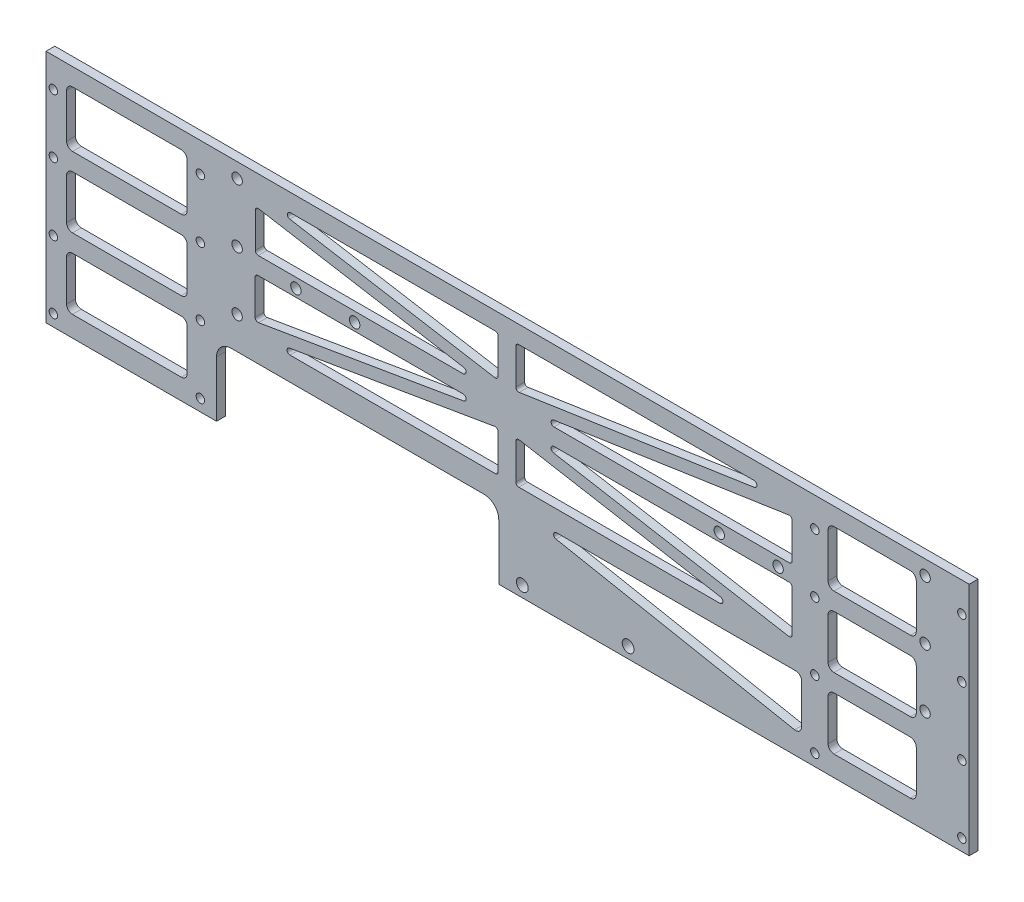
SolidWorks part; units mm, degrees
material "6061-T6 (SS)"
ref_plane "Front Plane" through (0, 0, 0) normal (0, 0, 1) x (1, 0, 0)
ref_plane "Top Plane" through (0, 0, 0) normal (0, 1, 0) x (1, 0, 0)
ref_plane "Right Plane" through (0, 0, 0) normal (1, 0, 0) x (0, 0, -1)
sketch "Sketch1" plane through (0, 0, 0) normal (0, 0, 1) x (1, 0, 0)
  line L1 (-199.39, 50.8) -> (199.39, 50.8)
  line L2 (-199.39, 50.8) -> (-199.39, -50.8)
  line L3 (-199.39, -50.8) -> (199.39, -50.8)
  line L4 (199.39, 50.8) -> (199.39, -50.8)
  line L5 (-199.39, 50.8) -> (199.39, -50.8) construction
  line L6 (-199.39, -50.8) -> (199.39, 50.8) construction
  point P0 (0, 0)
  dimension "D1" = 101.6
  dimension "D2" = 398.78
extrude "Boss-Extrude1" add sketch "Sketch1" along normal blind 3.81
sketch "Sketch11" plane through (0, 0, 3.81) normal (0, 0, 1) x (1, 0, 0)
  line L0 (-199.39, -50.8) -> (199.39, -50.8) construction
  line L1 (-125.73, -50.8) -> (-3.81, -50.8)
  line L2 (-125.73, -50.8) -> (-125.73, -20.32)
  line L3 (-125.73, -20.32) -> (-3.81, -20.32)
  line L4 (-3.81, -50.8) -> (-3.81, -20.32)
  line L5 (-199.39, 50.8) -> (-199.39, -50.8) construction
  line L6 (199.39, -50.8) -> (199.39, 50.8) construction
  dimension "D1" = 30.48
  dimension "D2" = 73.66
  dimension "D3" = 203.2
extrude "Cut-Extrude1" cut sketch "Sketch11" against normal through all
sketch "Sketch15" plane through (0, 0, 3.81) normal (0, 0, 1) x (1, 0, 0)
  line L0 (199.39, 50.8) -> (-199.39, 50.8) construction
  line L1 (91.44, 16.0648) -> (116.84, 16.0648) construction
  line L2 (180.34, 44.45) -> (180.34, -6.35) construction
  line L3 (199.39, -50.8) -> (199.39, 50.8) construction
  line L4 (199.39, 50.8) -> (-199.39, 50.8) construction
  line L5 (-199.39, 50.8) -> (-199.39, -50.8) construction
  line L6 (-66.04, 16.0648) -> (-91.44, 16.0648) construction
  line L7 (6.35, -46.0375) -> (52.07, -46.0375) construction
  line L8 (-3.81, -50.8) -> (199.39, -50.8) construction
  line L9 (-3.81, -50.8) -> (-3.81, -20.32) construction
  point P0 (196.215, 38.1)
  point P1 (196.215, 12.7)
  point P2 (196.215, -16.51)
  point P3 (196.215, -45.72)
  point P9 (132.715, -45.72)
  point P10 (180.34, 19.05)
  point P11 (132.715, -15.24)
  point P12 (132.715, 15.24)
  point P13 (132.715, 45.72)
  point P17 (91.44, 16.0648)
  point P20 (116.84, 16.0648)
  dimension "D1" = 63.5
  dimension "D2" = 3.175
  dimension "D3" = 29.21
  dimension "D4" = 29.21
  dimension "D5" = 25.4
  dimension "D6" = 5.08
  dimension "D7" = 30.48
  dimension "D8" = 30.48
  dimension "D9" = 30.48
  dimension "D10" = 19.05
  dimension "D11" = 50.8
  dimension "D12" = 6.35
  dimension "D13" = 25.4
  dimension "D14" = 34.7352
  dimension "D15" = 15.875
  dimension "D16" = 107.95
  dimension "D17" = 45.72
  dimension "D18" = 4.7625
  dimension "D19" = 10.16
hole_wizard "#6 Clearance Hole1" positions "Sketch19" profile "Sketch20" hole size "#6" standard "ANSI Inch" end condition through all
sketch "Sketch19" plane through (0, 0, 3.81) normal (0, 0, 1) x (1, 0, 0)
  line L0 (199.39, 50.8) -> (-199.39, 50.8) construction
  line L1 (199.39, -50.8) -> (199.39, 50.8) construction
  line L2 (-199.39, 50.8) -> (-199.39, -50.8) construction
  point P55 (132.715, -45.72)
  point P58 (196.215, -45.72)
  point P63 (132.715, 12.7)
  point P65 (132.715, -16.51)
  point P67 (196.215, 38.1)
  point P71 (196.215, -16.51)
  point P84 (-196.215, 38.1)
  point P86 (-196.215, 12.7)
  point P88 (-196.215, -16.51)
  point P90 (-196.215, -45.72)
  point P95 (-132.715, 38.1)
  point P97 (-132.715, 12.7)
  point P99 (-132.715, -16.51)
  point P101 (-132.715, -45.72)
  point P113 (196.215, 12.7)
  point P116 (132.715, 38.1)
  dimension "D2" = 12.7
  dimension "D3" = 29.21
  dimension "D4" = 25.4
  dimension "D5" = 29.21
  dimension "D6" = 25.4
  dimension "D7" = 29.21
  dimension "D8" = 29.21
  dimension "D9" = 3.175
  dimension "D10" = 12.7
  dimension "D11" = 12.7
  dimension "D12" = 25.4
  dimension "D13" = 29.21
  dimension "D14" = 29.21
  dimension "D15" = 3.175
  dimension "D16" = 12.7
  dimension "D17" = 25.4
  dimension "D18" = 29.21
  dimension "D19" = 29.21
  dimension "D20" = 66.675
  dimension "D21" = 66.675
sketch "Sketch20" plane through (132.715, -45.72, 3.81) normal (1, 0, 0) x (0, -1, 0)
  line L0 (0, 0) -> (0, 3.81)
  line L1 (0, 3.81) -> (1.8288, 3.81)
  line L2 (1.8288, 3.81) -> (1.8288, 0)
  line L5 (1.8288, 0) -> (0, 0)
  line L11 (0, -6.35) -> (0, 107.95) construction
  dimension "Thru Hole Dia." = 3.6576
  dimension "Thru Hole Depth" = 3.81
hole_wizard "#8 Clearance Hole1" positions "Sketch24" profile "Sketch25" hole size "#8" standard "ANSI Inch" end condition through all
sketch "Sketch24" plane through (0, 0, 3.81) normal (0, 0, 1) x (1, 0, 0)
  line L0 (-199.39, 50.8) -> (-199.39, -50.8) construction
  point P0 (180.34, 44.45)
  point P3 (180.34, 19.05)
  point P6 (180.34, -6.35)
  point P10 (-116.84, 44.45)
  point P12 (-116.84, 19.05)
  point P14 (-116.84, -6.35)
  point P23 (91.44, 16.0648)
  point P26 (116.84, 16.0648)
  point P29 (-91.44, 16.0648)
  point P32 (-66.04, 16.0648)
  dimension "D1" = 82.55
sketch "Sketch25" plane through (180.34, 44.45, 3.81) normal (1, 0, 0) x (0, -1, 0)
  line L0 (0, 0) -> (0, 3.81)
  line L1 (0, 3.81) -> (2.2479, 3.81)
  line L2 (2.2479, 3.81) -> (2.2479, 0)
  line L5 (2.2479, 0) -> (0, 0)
  line L11 (0, -6.35) -> (0, 107.95) construction
  dimension "Thru Hole Dia." = 4.4958
  dimension "Thru Hole Depth" = 3.81
fillet "Fillet1" radius 6.35 2 edges at (-125.73, -20.32, 1.905) (-3.81, -20.32, 1.905)
hole_wizard "#7 (0.201) Diameter Hole1" positions "Sketch26" profile "Sketch27" hole size "#7" standard "ANSI Inch" end condition through all
sketch "Sketch26" plane through (0, 0, 3.81) normal (0, 0, 1) x (1, 0, 0)
  point P0 (6.35, -46.0375)
  point P3 (52.07, -46.0375)
sketch "Sketch27" plane through (6.35, -46.0375, 3.81) normal (1, 0, 0) x (0, -1, 0)
  line L0 (0, 0) -> (0, 3.81)
  line L1 (0, 3.81) -> (2.5527, 3.81)
  line L2 (2.5527, 3.81) -> (2.5527, 0)
  line L5 (2.5527, 0) -> (0, 0)
  line L11 (0, -6.35) -> (0, 107.95) construction
  dimension "Thru Hole Dia." = 5.1054
  dimension "Thru Hole Depth" = 3.81
sketch "Sketch28" plane through (0, 0, 3.81) normal (0, 0, 1) x (1, 0, 0)
  line L0 (199.39, 50.8) -> (-199.39, 50.8) construction
  line L1 (-187.96, 43.18) -> (-140.97, 43.18)
  line L2 (-190.5, 40.64) -> (-190.5, 21.59)
  line L3 (-187.96, 19.05) -> (-140.97, 19.05)
  line L4 (-138.43, 40.64) -> (-138.43, 21.59)
  line L5 (-187.96, 11.43) -> (-140.97, 11.43)
  line L6 (-190.5, 8.89) -> (-190.5, -8.89)
  line L7 (-187.96, -11.43) -> (-140.97, -11.43)
  line L8 (-138.43, 8.89) -> (-138.43, -8.89)
  line L9 (-187.96, -19.05) -> (-140.97, -19.05)
  line L10 (-190.5, -21.59) -> (-190.5, -39.37)
  line L11 (-187.96, -41.91) -> (-140.97, -41.91)
  line L12 (-138.43, -21.59) -> (-138.43, -39.37)
  line L13 (-199.39, 50.8) -> (-199.39, -50.8) construction
  line L14 (140.97, 43.18) -> (173.99, 43.18)
  line L35 (138.43, 40.64) -> (138.43, 21.59)
  line L36 (140.97, 19.05) -> (173.99, 19.05)
  line L37 (176.53, 40.64) -> (176.53, 21.59)
  line L38 (140.97, 11.43) -> (173.99, 11.43)
  line L39 (138.43, 8.89) -> (138.43, -8.89)
  line L40 (140.97, -11.43) -> (173.99, -11.43)
  line L41 (176.53, 8.89) -> (176.53, -8.89)
  line L42 (140.97, -19.05) -> (173.99, -19.05)
  line L43 (138.43, -21.59) -> (138.43, -39.37)
  line L44 (140.97, -41.91) -> (173.99, -41.91)
  line L45 (176.53, -21.59) -> (176.53, -39.37)
  line L46 (199.39, -50.8) -> (199.39, 50.8) construction
  line L47 (127, -21.59) -> (127, -38.8367)
  line L48 (-107.4923, 37.7763) -> (-18.9532, 22.7697)
  line L49 (-19.1654, 20.2475) -> (-107.7046, 20.2475)
  line L50 (-108.9746, 21.5175) -> (-108.9746, 36.5242)
  line L51 (-10.16, -20.32) -> (-119.38, -20.32) construction
  line L52 (-4.0726, 41.91) -> (-4.0726, 26.9034)
  line L53 (-5.5548, 25.6512) -> (-94.0939, 40.6579)
  line L54 (-5.3426, 43.18) -> (-93.8817, 43.18)
  line L55 (123.9817, -41.3313) -> (20.9058, -21.5673)
  line L56 (21.145, -19.05) -> (124.46, -19.05)
  line L58 (-5.3426, -10.16) -> (-93.9886, -10.16)
  line L60 (-109.0991, 11.43) -> (-109.0991, -3.5769)
  line L61 (-107.8291, 12.7) -> (-19.1831, 12.7)
  line L62 (-107.6171, -4.8291) -> (-18.9711, 10.1778)
  line L63 (-4.0726, -8.89) -> (-4.0726, 6.1169)
  line L64 (-94.2005, -7.6378) -> (-5.5545, 7.3691)
  line L65 (121.6574, 19.9686) -> (20.0574, 19.9686)
  line L66 (3.5474, 41.91) -> (3.5474, 26.6559)
  line L67 (4.8174, 43.18) -> (106.4174, 43.18)
  line L68 (5.006, 25.4) -> (106.606, 40.6541)
  line L69 (122.9274, 21.2386) -> (122.9274, 36.4927)
  line L70 (19.8689, 22.4946) -> (121.4689, 37.7486)
  line L71 (5.0371, 7.62) -> (91.9491, -7.6391)
  line L72 (91.7295, -10.16) -> (4.8174, -10.16)
  line L73 (3.5474, -8.89) -> (3.5474, 6.3691)
  line L74 (122.9274, 11.43) -> (122.9274, -6.4079)
  line L75 (121.4378, -7.6588) -> (19.8378, 10.1791)
  line L76 (121.6574, 12.7) -> (20.0574, 12.7)
  arc A0 (138.43, 21.59) -> (140.97, 19.05) centre (140.97, 21.59) ccw
  arc A1 (140.97, 43.18) -> (138.43, 40.64) centre (140.97, 40.64) ccw
  arc A2 (176.53, 40.64) -> (173.99, 43.18) centre (173.99, 40.64) ccw
  arc A3 (176.53, 21.59) -> (173.99, 19.05) centre (173.99, 21.59) cw
  arc A4 (173.99, -11.43) -> (176.53, -8.89) centre (173.99, -8.89) ccw
  arc A5 (173.99, 11.43) -> (176.53, 8.89) centre (173.99, 8.89) cw
  arc A6 (138.43, 8.89) -> (140.97, 11.43) centre (140.97, 8.89) cw
  arc A7 (140.97, -11.43) -> (138.43, -8.89) centre (140.97, -8.89) cw
  arc A8 (176.53, -21.59) -> (173.99, -19.05) centre (173.99, -21.59) ccw
  arc A9 (176.53, -39.37) -> (173.99, -41.91) centre (173.99, -39.37) cw
  arc A10 (138.43, -39.37) -> (140.97, -41.91) centre (140.97, -39.37) ccw
  arc A11 (140.97, -19.05) -> (138.43, -21.59) centre (140.97, -21.59) ccw
  arc A32 (-190.5, -39.37) -> (-187.96, -41.91) centre (-187.96, -39.37) ccw
  arc A33 (-138.43, -39.37) -> (-140.97, -41.91) centre (-140.97, -39.37) cw
  arc A34 (-138.43, -21.59) -> (-140.97, -19.05) centre (-140.97, -21.59) ccw
  arc A35 (-187.96, -19.05) -> (-190.5, -21.59) centre (-187.96, -21.59) ccw
  arc A36 (-190.5, -8.89) -> (-187.96, -11.43) centre (-187.96, -8.89) ccw
  arc A37 (-140.97, -11.43) -> (-138.43, -8.89) centre (-140.97, -8.89) ccw
  arc A38 (-138.43, 8.89) -> (-140.97, 11.43) centre (-140.97, 8.89) ccw
  arc A39 (-187.96, 11.43) -> (-190.5, 8.89) centre (-187.96, 8.89) ccw
  arc A40 (-190.5, 21.59) -> (-187.96, 19.05) centre (-187.96, 21.59) ccw
  arc A41 (-138.43, 21.59) -> (-140.97, 19.05) centre (-140.97, 21.59) cw
  arc A42 (-138.43, 40.64) -> (-140.97, 43.18) centre (-140.97, 40.64) ccw
  arc A43 (-187.96, 43.18) -> (-190.5, 40.64) centre (-187.96, 40.64) ccw
  arc A44 (-19.1654, 20.2475) -> (-18.9532, 22.7697) centre (-19.1654, 21.5175) ccw
  arc A45 (-5.5548, 25.6512) -> (-4.0726, 26.9034) centre (-5.3426, 26.9034) ccw
  arc A46 (-4.0726, 41.91) -> (-5.3426, 43.18) centre (-5.3426, 41.91) ccw
  arc A47 (-108.9746, 21.5175) -> (-107.7046, 20.2475) centre (-107.7046, 21.5175) ccw
  arc A48 (-107.4923, 37.7763) -> (-108.9746, 36.5242) centre (-107.7046, 36.5242) ccw
  arc A49 (-93.8817, 43.18) -> (-94.0939, 40.6579) centre (-93.8817, 41.91) ccw
  arc A50 (-93.9886, -10.16) -> (-94.2005, -7.6378) centre (-93.9886, -8.89) cw
  arc A51 (-4.0726, -8.89) -> (-5.3426, -10.16) centre (-5.3426, -8.89) cw
  arc A52 (-4.0726, 6.1169) -> (-5.5545, 7.3691) centre (-5.3426, 6.1169) ccw
  arc A53 (-19.1831, 12.7) -> (-18.9711, 10.1778) centre (-19.1831, 11.43) cw
  arc A54 (-109.0991, 11.43) -> (-107.8291, 12.7) centre (-107.8291, 11.43) cw
  arc A55 (-107.6171, -4.8291) -> (-109.0991, -3.5769) centre (-107.8291, -3.5769) cw
  arc A56 (20.0574, 19.9686) -> (19.8689, 22.4946) centre (20.0574, 21.2386) cw
  arc A57 (122.9274, 21.2386) -> (121.6574, 19.9686) centre (121.6574, 21.2386) cw
  arc A58 (122.9274, 36.4927) -> (121.4689, 37.7486) centre (121.6574, 36.4927) ccw
  arc A59 (106.4174, 43.18) -> (106.606, 40.6541) centre (106.4174, 41.91) cw
  arc A60 (3.5474, 41.91) -> (4.8174, 43.18) centre (4.8174, 41.91) cw
  arc A61 (5.006, 25.4) -> (3.5474, 26.6559) centre (4.8174, 26.6559) cw
  arc A62 (91.7295, -10.16) -> (91.9491, -7.6391) centre (91.7295, -8.89) ccw
  arc A63 (121.4378, -7.6588) -> (122.9274, -6.4079) centre (121.6574, -6.4079) ccw
  arc A64 (122.9274, 11.43) -> (121.6574, 12.7) centre (121.6574, 11.43) ccw
  arc A65 (3.5474, -8.89) -> (4.8174, -10.16) centre (4.8174, -8.89) ccw
  arc A66 (5.0371, 7.62) -> (3.5474, 6.3691) centre (4.8174, 6.3691) ccw
  arc A67 (20.0574, 12.7) -> (19.8378, 10.1791) centre (20.0574, 11.43) ccw
  arc A68 (21.145, -19.05) -> (20.9058, -21.5673) centre (21.145, -20.32) ccw
  arc A69 (127, -38.8367) -> (123.9817, -41.3313) centre (124.46, -38.8367) cw
  arc A70 (127, -21.59) -> (124.46, -19.05) centre (124.46, -21.59) ccw
  point P16 (-138.43, 31.115)
  point P53 (-109.0991, -10.16)
  point P58 (138.43, 43.18)
  point P61 (176.53, 43.18)
  point P64 (176.53, 19.05)
  point P67 (176.53, -11.43)
  point P70 (176.53, 11.43)
  point P73 (138.43, 11.43)
  point P78 (176.53, -19.05)
  point P81 (176.53, -41.91)
  point P86 (138.43, -19.05)
  point P89 (-4.0726, -10.16)
  point P92 (-4.0726, 7.62)
  point P105 (7.7774, 43.18)
  point P108 (7.7774, 20.32)
  point P111 (7.7774, 12.7)
  point P114 (7.7774, -10.16)
  point P115 (-4.0726, 12.7)
  point P118 (-109.0991, 12.7)
  point P126 (-109.0991, -5.08)
  point P127 (-109.0991, -10.16)
  point P130 (-109.0991, 12.7)
  point P131 (-4.0726, 20.2475)
  point P134 (-4.0726, 25.4)
  point P139 (-190.5, -41.91)
  point P146 (-190.5, -19.05)
  point P149 (-190.5, -11.43)
  point P156 (-190.5, 11.43)
  point P165 (-4.0726, 43.18)
  point P168 (-108.9746, 20.2475)
  point P171 (-108.9746, 38.0275)
  point P174 (-108.9746, 43.18)
  point P179 (3.5474, 31.9034)
  point P180 (-39.8842, 54.7634)
  dimension "D42" = 2.54
  dimension "D43" = 1.27
  dimension "D34" = 1.27
  dimension "D22" = 1.27
  dimension "D35" = 1.27
  dimension "D46" = 1.27
  dimension "D52" = 2.54
  dimension "D1" = 7.62
  dimension "D2" = 31.75
  dimension "D3" = 8.89
  dimension "D4" = 60.96
  dimension "D5" = 7.62
  dimension "D6" = 8.89
  dimension "D7" = 60.96
  dimension "D8" = 8.89
  dimension "D9" = 60.96
  dimension "D10" = 7.62
  dimension "D11" = 22.86
  dimension "D12" = 22.86
  dimension "D13" = 7.62
  dimension "D14" = 7.62
  dimension "D15" = 24.13
  dimension "D16" = 22.86
  dimension "D17" = 22.86
  dimension "D18" = 38.1
  dimension "D19" = 38.1
  dimension "D20" = 38.1
  dimension "D21" = 7.62
  dimension "D23" = 17.78
  dimension "D24" = 7.62
  dimension "D25" = 7.62
  dimension "D26" = 17.78
  dimension "D27" = 22.86
  dimension "D28" = 17.78
  dimension "D29" = 22.86
  dimension "D30" = 119.38
  dimension "D31" = 17.78
  dimension "D32" = 104.902
  dimension "D33" = 104.902
  dimension "D36" = 22.86
  dimension "D37" = 22.86
  dimension "D38" = 22.86
  dimension "D39" = 5.08
  dimension "D40" = 17.78
  dimension "D41" = 5.08
  dimension "D44" = 101.6
  dimension "D45" = 101.6
  dimension "D47" = 7.62
  dimension "D48" = 17.78
  dimension "D49" = 119.38
  dimension "D50" = 88.646
  dimension "D51" = 101.6
  dimension "D53" = 10.16
  dimension "D54" = 5.08
extrude "Cut-Extrude2" cut sketch "Sketch28" against normal through all
